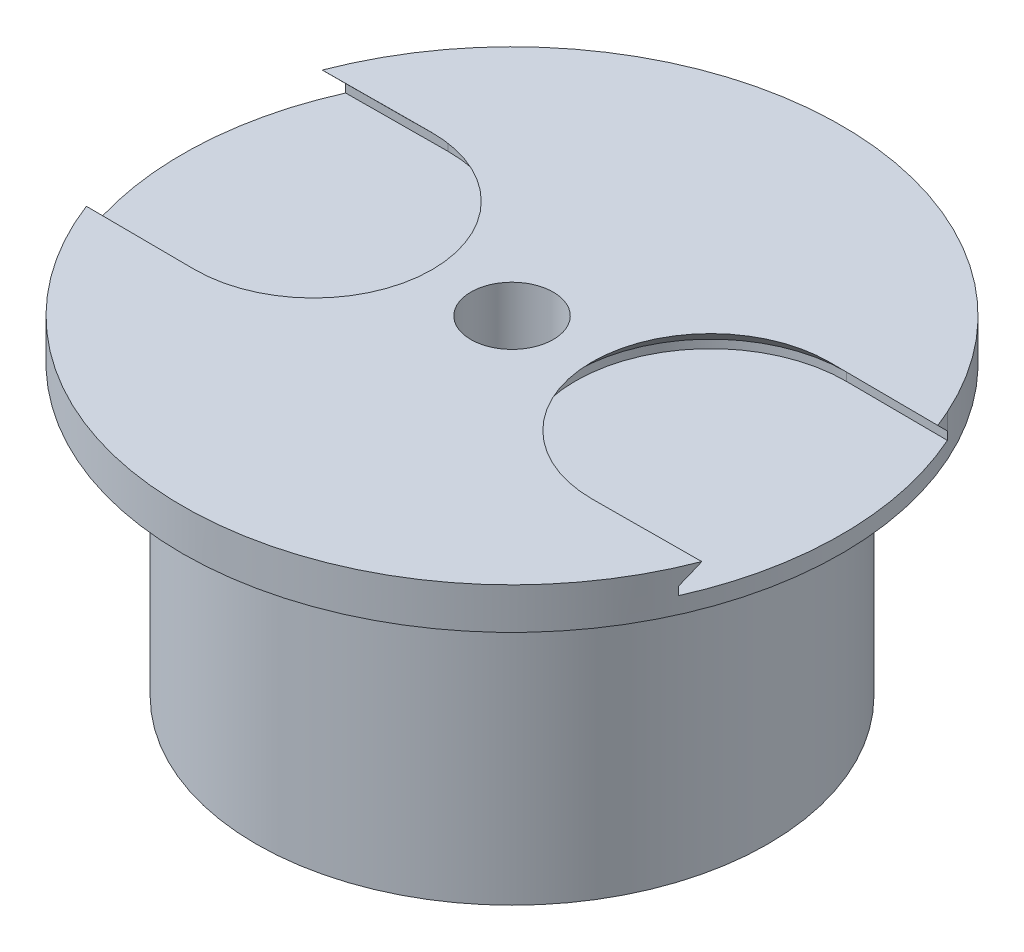
SolidWorks part; units mm, degrees
ref_plane "Front Plane" through (0, 0, 0) normal (0, 0, 1) x (1, 0, 0)
ref_plane "Top Plane" through (0, 0, 0) normal (0, 1, 0) x (1, 0, 0)
ref_plane "Right Plane" through (0, 0, 0) normal (1, 0, 0) x (0, 0, -1)
sketch "Sketch1" plane through (0, 0, 0) normal (0, 1, 0) x (1, 0, 0)
  circle A0 centre (0, 0) radius 31.06
  circle A1 centre (0, 0) radius 5
  dimension "D1" = 62.12
  dimension "D2" = 10
extrude "Boss-Extrude1" add sketch "Sketch1" along normal blind 35
sketch "Sketch18" plane through (0, 0, 0) normal (0, -1, 0) x (1, 0, 0)
  circle A0 centre (0, 0) radius 7.5
  circle A1 centre (0, 0) radius 28.66
  circle A2 centre (0, 0) radius 31.06 construction
  circle A3 centre (0, 0) radius 5 construction
  dimension "D1" = 2.4
  dimension "D2" = 2.5
extrude "Cut-Extrude12" cut sketch "Sketch18" against normal blind 13
sketch "Sketch19" plane through (0, 0, 0) normal (0, -1, 0) x (1, 0, 0)
  circle A0 centre (0, 0) radius 7.5 construction
  circle A1 centre (0, 0) radius 7.5
curve "Helix/Spiral1" pitch 12 height 12 radius 7.5 centre (0, 0, 0) axis (0, 1, 0) start towards (0, 0, -1)
sketch "Sketch20" plane through (0, 0, 0) normal (1, 0, 0) x (0, 0, -1)
  line L1 (-7.5, 0) -> (7.5, 0) construction
  line L2 (7.5, -0.6294) -> (7.5, 0.6294)
  line L4 (7.5, 0.6294) -> (8.5, 0.3457)
  line L5 (8.5, 0.3457) -> (8.5, -0.3956)
  line L6 (8.5, -0.3956) -> (7.5, -0.6294)
  line L7 (8, -0.5125) -> (8, 0.4875)
  line L8 (-7.5, 0) -> (7.5, 0)
  dimension "D1" = 1
  dimension "D2" = 29
  dimension "D3" = 1
sweep "Sweep2" add profiles "Sketch20" path "Helix/Spiral1"
pattern_circular "CirPattern8" count 4 over 360 about axis through (0, 0, 0) along (0, -1, 0) of "Sweep2"
sketch "Sketch24" plane through (0, 0, 0) normal (0, 0, 1) x (1, 0, 0)
  line L1 (-31.06, 0) -> (31.06, 0) construction
  line L2 (-31.06, 0) -> (-28.66, 0)
  line L3 (-31.06, 0) -> (-28.66, 2.4)
  line L5 (-28.66, 0) -> (-28.66, 2.4)
  line L6 (28.66, 0) -> (31.06, 0)
  dimension "D1" = 45
ref_axis "Axis1" through (0, 35, 0) along (0, -1, 0)
revolve "Cut-Revolve1" cut sketch "Sketch24" angle 360 about axis through (0, 35, 0) along (0, -1, 0)
sketch "Sketch25" plane through (0, 35, 0) normal (0, 1, 0) x (1, 0, 0)
sketch "Sketch28" plane through (0, 13, 0) normal (0, -1, 0) x (1, 0, 0)
  circle A0 centre (0, 0) radius 7.5 construction
  circle A1 centre (0, 0) radius 28.66
  circle A2 centre (0, 0) radius 28.66
  circle A3 centre (0, 0) radius 7.5
  dimension "D1" = 0
extrude "Cut-Extrude14" cut sketch "Sketch28" against normal blind 17 draft 32
sketch "Sketch30" plane through (0, 35, 0) normal (0, 1, 0) x (1, 0, 0)
  circle A0 centre (0, 0) radius 5 construction
  circle A2 centre (0, 0) radius 40
  circle A3 centre (0, 0) radius 5
  dimension "D1" = 80
extrude "Boss-Extrude2" add sketch "Sketch30" along normal blind 5
sketch "Sketch31" plane through (0, 40, 0) normal (0, 1, 0) x (1, 0, 0)
  line L0 (40, 0) -> (-40, 0)
  line L1 (40, 13.3) -> (40, -13.3)
  line L2 (40, -13.3) -> (24.1845, -13.3997)
  line L3 (40, 13.3) -> (16.7999, 13.4463)
  line L4 (0, -40) -> (0, 40)
  line L5 (-40, 13.3) -> (-16.7999, 13.4463)
  line L6 (-40, -13.3) -> (-24.1845, -13.3997)
  line L7 (-40, 13.3) -> (-40, -13.3)
  circle A0 centre (0, 0) radius 40 construction
  circle A1 centre (24.1, 0) radius 13.4
  circle A2 centre (-24.1, 0) radius 13.4
  circle M2 centre (0, 0) radius 40
  dimension "D1" = 26.8
  dimension "D2" = 26.6
  dimension "D3" = 15.9
extrude "Cut-Extrude16" cut sketch "Sketch31" against normal blind 1 from offset 2 contours A2 L0 | A2 L0 | L0 A2 L5 M2 | L6 A2 L0 M2 | A1 L0 | L0 A1 | A1 L2 L0 M2 | A1 L0 L3 M2 | A1 region at (36.0401, 40, 8.4076) region at (36.0401, 40, -8.4076) region at (24.1, 40, 5.6871) region at (24.1, 40, -5.6871) region at (-36.0401, 40, -8.4076) region at (-36.0401, 40, 8.4076) region at (-24.1, 40, 5.6871) region at (-24.1, 40, -5.6871) offset against normal yes
sketch "Sketch32" plane through (0, 40, 0) normal (0, 1, 0) x (1, 0, 0)
  line L0 (37.7191, 13.3144) -> (37.7191, -13.3144)
  line L1 (0, -40) -> (0, 40) construction
  line L2 (37.7191, 13.3144) -> (24.1845, 13.3997)
  line L3 (24.1845, -13.3997) -> (37.7191, -13.3144)
  line L4 (37.7191, 13.3144) -> (24.1845, 13.3997)
  line L5 (24.1845, -13.3997) -> (37.7191, -13.3144)
  line L6 (-24.1845, 13.3997) -> (-37.7191, 13.3144)
  line L7 (-37.7191, -13.3144) -> (-24.1845, -13.3997)
  line L8 (0, -40) -> (0, 40)
  line L9 (-24.1, -12) -> (-38.1576, -12)
  line L10 (31.06, 0) -> (24.1, 0)
  line L11 (-24.1, 12) -> (-38.1576, 12)
  line L12 (-31.06, 0) -> (-24.1, 0)
  line L13 (-24.1845, -13.3997) -> (-37.7191, -13.3144)
  line L14 (24.1, 12) -> (38.1576, 12)
  line L15 (24.1, -12) -> (38.1576, -12)
  line L16 (-37.7191, 13.3144) -> (-24.1845, 13.3997)
  line L17 (-37.7191, 13.3144) -> (-37.7191, -13.3144)
  circle A0 centre (24.1, 0) radius 12
  arc A1 (-24.1845, 13.3997) -> (-24.1845, -13.3997) centre (-24.1, 0) cw
  arc A2 (24.1845, 13.3997) -> (24.1845, -13.3997) centre (24.1, 0) ccw
  arc A3 (37.7191, -13.3144) -> (37.7191, 13.3144) centre (0, 0) ccw
  arc A4 (24.1845, 13.3997) -> (24.1845, -13.3997) centre (24.1, 0) ccw
  arc A5 (-37.7191, -13.3144) -> (37.7191, 13.3144) centre (0, 0) ccw
  arc A6 (-24.1845, -13.3997) -> (-24.1845, 13.3997) centre (-24.1, 0) ccw
  arc A7 (-37.7191, 13.3144) -> (-37.7191, -13.3144) centre (0, 0) ccw
  circle A8 centre (-24.1, 0) radius 12
  arc A9 (37.7191, 13.3144) -> (-37.7191, -13.3144) centre (0, 0) ccw
  circle M9 centre (0, 0) radius 40
  dimension "D4" = 24
  dimension "D1" = 0
  dimension "D2" = 0
extrude "Cut-Extrude17" cut sketch "Sketch32" against normal up to next contours A8 | L9 A8 L11 L17 | L17 L11 L9 M9 | A0 | A0 L15 L0 L14 | L0 L15 L14 M9 region at (38.6449, 40, 0) region at (37.4431, 40, 0) region at (32.3453, 40, -8.2453) region at (-38.6449, 40, 0) region at (-30.9095, 40, -11.7241) region at (-15.8547, 40, -8.2453)
ref_plane "Plane2" through (40, 0, 0) normal (1, 0, 0) x (0, 0, -1)
sketch "Sketch33" plane through (0, 37, 0) normal (0, 1, 0) x (1, 0, 0)
  line L0 (0, -40) -> (0, 40) construction
  line L1 (0, -40) -> (0, 40)
  line L2 (24.1845, -13.3997) -> (37.7191, -13.3144)
  line L3 (37.7191, 13.3144) -> (24.1845, 13.3997)
  line L4 (24.1845, -13.3997) -> (40, -13.3)
  line L5 (40, 13.3) -> (24.1845, 13.3997)
  line L6 (40, -40) -> (40, 40)
  line L7 (-40, -40) -> (-40, 40)
  line L8 (-40, 13.3) -> (-24.1845, 13.3997)
  line L9 (-24.1845, -13.3997) -> (-40, -13.3)
  arc A0 (-37.7191, -13.3144) -> (-37.7191, 13.3144) centre (0, 0) cw
  arc A1 (-24.1845, 13.3997) -> (-24.1845, -13.3997) centre (-24.1, 0) cw
  arc A2 (24.1845, 13.3997) -> (24.1845, -13.3997) centre (24.1, 0) ccw
  arc A3 (37.7191, -13.3144) -> (37.7191, 13.3144) centre (0, 0) ccw
  arc A4 (24.1845, 13.3997) -> (24.1845, -13.3997) centre (24.1, 0) ccw
  arc A5 (37.7191, -13.3144) -> (37.7191, 13.3144) centre (0, 0) ccw
  dimension "D1" = 0
  dimension "D2" = 40
sketch "Sketch34" plane through (40, 0, 0) normal (1, 0, 0) x (0, 0, -1)
  line L0 (-40, 37) -> (40, 37) construction
  line L1 (-40, 37) -> (40, 37)
  line L2 (-13.3997, 37) -> (-13.3, 37) construction
  line L3 (-13.3997, 37) -> (-13.3, 37)
  line L4 (-13.3, 37) -> (-16.3, 37)
  line L5 (-16.3, 37) -> (-16.3, 38)
  line L6 (-16.3, 38) -> (-13.3, 41)
  line L7 (-13.3, 41) -> (-13.3, 37)
  line L8 (-13.3144, 37) -> (-13.3144, 38) construction
  dimension "D1" = 3
  dimension "D2" = 45
sweep "Cut-Sweep1" cut profiles "Sketch34" path "Sketch33"
sketch "Sketch35" plane through (0, 40, 0) normal (0, 1, 0) x (1, 0, 0)
  line L4 (37.7191, 13.3144) -> (24.1845, 13.3997)
  line L5 (24.1845, -13.3997) -> (37.7191, -13.3144)
  line L6 (38.1576, -12) -> (24.1, -12)
  line L7 (24.1, 12) -> (38.1576, 12)
  line L8 (37.7191, 13.3144) -> (24.1845, 13.3997)
  line L9 (24.1845, -13.3997) -> (37.7191, -13.3144)
  line L10 (38.1576, -12) -> (24.1, -12)
  line L11 (24.1, 12) -> (38.1576, 12)
  arc A4 (24.1845, 13.3997) -> (24.1845, -13.3997) centre (24.1, 0) ccw
  arc A5 (37.7191, -13.3144) -> (38.1576, -12) centre (0, 0) ccw
  arc A6 (24.1, 12) -> (24.1, -12) centre (24.1, 0) ccw
  arc A7 (38.1576, 12) -> (37.7191, 13.3144) centre (0, 0) ccw
  arc A8 (24.1845, 13.3997) -> (24.1845, -13.3997) centre (24.1, 0) ccw
  arc A9 (37.7191, -13.3144) -> (38.1576, -12) centre (0, 0) ccw
  arc A10 (24.1, 12) -> (24.1, -12) centre (24.1, 0) ccw
  arc A11 (38.1576, 12) -> (37.7191, 13.3144) centre (0, 0) ccw
  dimension "D1" = 0
extrude "Cut-Extrude19" cut sketch "Sketch35" against normal blind 2
ref_plane "Plane3" through (-40, 0, 0) normal (-1, 0, 0) x (0, 0, 1)
sketch "Sketch37" plane through (-40, 0, 0) normal (-1, 0, 0) x (0, 0, 1)
  line L0 (40, 37) -> (-40, 37) construction
  line L1 (40, 37) -> (-40, 37)
  line L2 (-13.3, 37) -> (-13.3997, 37) construction
  line L3 (-13.3, 37) -> (-13.3997, 37)
  line L4 (-13.3, 37) -> (-16.3, 37)
  line L5 (-16.3, 37) -> (-16.3, 38)
  line L6 (-16.3, 38) -> (-13.3, 41)
  line L7 (-13.3, 41) -> (-13.3, 37)
  line L8 (-13.3144, 37) -> (-13.3144, 38) construction
  dimension "D1" = 45
  dimension "D2" = 3
sweep "Cut-Sweep2" cut profiles "Sketch37" path "Sketch33<3>" body kept at (0, -0.6295, -7.4997) body kept at (-24.1845, 40, -13.3997)
sketch "Sketch33<3>" plane through (0, 37, 0) normal (0, 1, 0) x (1, 0, 0) same geometry as "Sketch33"
sketch "Sketch38" plane through (0, 40, 0) normal (0, 1, 0) x (1, 0, 0)
  line L4 (-37.7191, -13.3144) -> (-24.1845, -13.3997)
  line L5 (-24.1845, 13.3997) -> (-37.7191, 13.3144)
  line L6 (-38.1576, 12) -> (-24.1, 12)
  line L7 (-24.1, -12) -> (-38.1576, -12)
  line L8 (-37.7191, -13.3144) -> (-24.1845, -13.3997)
  line L9 (-24.1845, 13.3997) -> (-37.7191, 13.3144)
  line L10 (-38.1576, 12) -> (-24.1, 12)
  line L11 (-24.1, -12) -> (-38.1576, -12)
  arc A4 (-24.1845, -13.3997) -> (-24.1845, 13.3997) centre (-24.1, 0) ccw
  arc A5 (-37.7191, 13.3144) -> (-38.1576, 12) centre (0, 0) ccw
  arc A6 (-24.1, -12) -> (-24.1, 12) centre (-24.1, 0) ccw
  arc A7 (-38.1576, -12) -> (-37.7191, -13.3144) centre (0, 0) ccw
  arc A8 (-24.1845, -13.3997) -> (-24.1845, 13.3997) centre (-24.1, 0) ccw
  arc A9 (-37.7191, 13.3144) -> (-38.1576, 12) centre (0, 0) ccw
  arc A10 (-24.1, -12) -> (-24.1, 12) centre (-24.1, 0) ccw
  arc A11 (-38.1576, -12) -> (-37.7191, -13.3144) centre (0, 0) ccw
  dimension "D1" = 0
extrude "Cut-Extrude20" cut sketch "Sketch38" against normal blind 2
